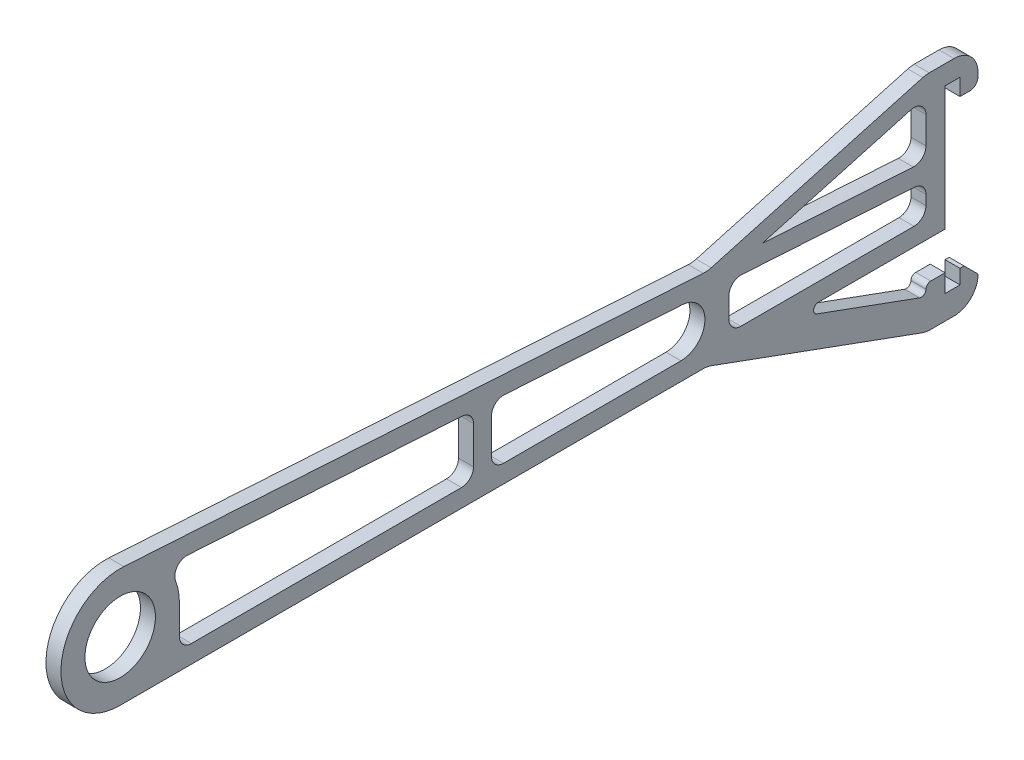
SolidWorks part; units mm, degrees
material "Delrin"
ref_plane "Front Plane" through (0, 0, 0) normal (0, 0, 1) x (1, 0, 0)
ref_plane "Top Plane" through (0, 0, 0) normal (0, 1, 0) x (1, 0, 0)
ref_plane "Right Plane" through (0, 0, 0) normal (1, 0, 0) x (0, 0, -1)
sketch "Sketch1" plane through (0, 0, 0) normal (1, 0, 0) x (0, 0, -1)
  line L0 (0.3859, 6.2619) -> (62.1851, 2.453)
  line L1 (0, -6.2738) -> (62.1851, -6.2738)
  line L2 (85.344, 8.8996) -> (88.3158, 8.8996)
  line L3 (4.7629, 4.0835) -> (85.344, -0.883)
  line L4 (4.5027, -4.3688) -> (85.344, -4.3688)
  line L5 (4.101, 4.1243) -> (87.7175, -1.0293) construction
  line L6 (0, -4.3688) -> (85.344, -4.3688) construction
  line L7 (85.344, -6.2738) -> (85.344, 8.8996) construction
  line L16 (6.2738, 0) -> (6.2738, -4.3688)
  line L17 (39.3251, 1.9533) -> (39.3251, -4.3688)
  line L18 (37.4201, 2.0707) -> (37.4201, -4.3688)
  line L23 (4.2182, 6.0257) -> (87.8347, 0.8721) construction
  line L24 (89.9668, 5.0896) -> (88.9508, 5.0896)
  line L25 (88.9508, 5.0896) -> (88.9508, 6.8676)
  line L26 (88.9508, 6.8676) -> (87.376, 6.8676)
  line L27 (87.376, 6.8676) -> (87.376, -6.2738)
  line L28 (87.376, -12.1824) -> (88.9508, -12.1824)
  line L29 (88.9508, -12.1824) -> (88.9508, -10.6584)
  line L30 (88.9508, -10.6584) -> (89.3826, -10.6584)
  line L31 (90.8558, -12.1316) -> (90.8558, -12.1824)
  line L32 (88.3158, -14.7224) -> (85.344, -14.7224)
  line L33 (85.344, -14.7224) -> (85.344, -6.2738) construction
  line L34 (90.8558, 5.9786) -> (90.8558, 6.3596)
  line L35 (89.3826, -10.6584) -> (90.8558, -12.1316)
  line L36 (64.4711, 0.4035) -> (64.4711, -4.3688)
  line L37 (62.1851, 0.5444) -> (62.1851, -4.3688)
  line L38 (62.1851, 2.453) -> (85.344, 8.8996)
  line L39 (68.0011, 2.0945) -> (85.344, 6.9222)
  line L40 (62.1851, -6.2738) -> (85.344, -14.7224)
  line L41 (71.0788, -6.2738) -> (85.344, -11.4779)
  line L42 (63.2297, -3.4104) -> (86.3886, -11.859) construction
  line L43 (62.696, 0.6178) -> (85.8549, 7.0644) construction
  line L44 (71.0788, -6.2738) -> (85.344, -6.2738)
  line L45 (0, -6.2738) -> (85.344, -6.2738) construction
  line L46 (68.0011, 2.0945) -> (85.344, 1.0256)
  line L47 (62.1851, -4.3688) -> (62.1851, 49995.6312) construction
  line L48 (85.344, 6.9222) -> (85.344, 1.0256)
  line L49 (85.344, -0.883) -> (85.344, -4.3688)
  line L50 (87.376, -12.1824) -> (87.376, -10.2774)
  line L51 (85.344, -6.2738) -> (87.376, -6.2738)
  line L52 (87.376, -10.2774) -> (85.344, -10.2774)
  line L53 (85.344, -10.2774) -> (85.344, -11.4779)
  circle A0 centre (0, 0) radius 3.7338
  circle A1 centre (0, 0) radius 6.2738
  arc A2 (88.3158, 8.8996) -> (90.8558, 6.3596) centre (88.3158, 6.3596) cw
  arc A3 (90.8558, -12.1824) -> (88.3158, -14.7224) centre (88.3158, -12.1824) cw
  arc A4 (90.8558, 5.9786) -> (89.9668, 5.0896) centre (89.9668, 5.9786) cw
  point P47 (90.8558, 8.8996)
  point P50 (90.8558, -14.7224)
  point P53 (90.8558, 5.0896)
  point P54 (90.8558, -10.6584)
  point P56 (90.8558, -10.6584)
  dimension "D1" = 7.4676
  dimension "D2" = 2.54
  dimension "D3" = 5.842
  dimension "D8" = 1.5748
  dimension "D18" = 2.54
  dimension "D19" = 2.54
  dimension "D20" = 0.889
  dimension "D21" = 22.86
  dimension "D5" = 37.4201
  dimension "D10" = 1.905
  dimension "D11" = 1.778
  dimension "D12" = 1.905
  dimension "D4" = 5.3842
  dimension "D9" = 1.5748
  dimension "D14" = 1.524
  dimension "D15" = 3.81
  dimension "D16" = 4.064
  dimension "D17" = 1.905
  dimension "D22" = 19.05
  dimension "D23" = 85.344
  dimension "D24" = 2.032
  dimension "D25" = 2.286
  dimension "D29" = 1.905
  dimension "D6" = 1.905
  dimension "D7" = 1.905
  dimension "D27" = 3.048
  dimension "D28" = 1.905
extrude "Boss-Extrude1" add sketch "Sketch1" along normal blind 1.5875 contours A1 L1 | A1 L4 L16 | L3 L18 L4 L17 | L31 L30 L29 L28 L27 L26 L25 L24 A4 L34 A2 L2 L7 L33 L32 A3 | A1 A0 | L3 L37 L4 L36 region at (0, 3.4205, -31.2278) region at (0, 5.4578, -2.7163) region at (0, -1.1783, -38.3697) region at (0, -3.3098, -5.7584) region at (0, -1.9473, -63.3226)
sketch "Sketch2" plane through (0, 0, -87.376) normal (0, 0, -1) x (-1, 0, 0)
  line L0 (-1.5875, 8.8996) -> (0, 8.8996) construction
  line L1 (-1.5875, 6.8676) -> (0, 6.8676) construction
  line L2 (-1.5875, -12.1824) -> (0, -12.1824) construction
  line L3 (-1.5875, -14.7224) -> (0, -14.7224) construction
  line L4 (-1.5875, 8.8996) -> (0, 8.8996)
  line L5 (-1.5875, 6.8676) -> (0, 6.8676)
  line L6 (-1.5875, -12.1824) -> (0, -12.1824)
  line L7 (-1.5875, -14.7224) -> (0, -14.7224)
  line L8 (-1.5875, 8.8996) -> (-1.5875, 6.8676)
  line L9 (0, 8.8996) -> (0, 6.8676)
  line L10 (-1.5875, -12.1824) -> (-1.5875, -14.7224)
  line L11 (0, -12.1824) -> (0, -14.7224)
fillet "Fillet1" radius 2.54 4 edges at (0.7937, 2.453, -62.1851) (0.7937, 8.8996, -85.344) (0.7937, -6.2738, -62.1851) (0.7937, -14.7224, -85.344)
fillet "Fillet2" radius 1.27 12 edges at (0.7937, 4.0835, -4.7629) (0.7937, -4.3688, -6.2738) (0.7937, -4.3688, -37.4201) (0.7937, 2.0707, -37.4201) (0.7937, -4.3688, -39.3251) (0.7937, 1.9533, -39.3251) (0.7937, 0.4035, -64.4711) (0.7937, -4.3688, -64.4711) (0.7937, 1.0256, -85.344) (0.7937, 6.9222, -85.344) (0.7937, -0.883, -85.344) (0.7937, -4.3688, -85.344)
fillet "Fillet3" radius 0.508 2 edges at (0.7937, -6.2738, -71.0788) (0.7937, -11.4779, -85.344)
fillet "Fillet4" radius 0.508 1 edges at (0.7937, -10.2774, -85.344)
sketch "Sketch4" plane through (1.5875, 0, 0) normal (1, 0, 0) x (0, 0, -1)
  line L0 (40.6732, 1.8702) -> (62.1851, 0.5444) construction
  line L1 (62.1851, 0.5444) -> (62.1851, -4.3688) construction
  line L2 (40.5951, -4.3688) -> (62.1851, -4.3688) construction
  line L3 (59.5471, 0.707) -> (62.1851, 0.5444)
  line L4 (62.1851, 0.5444) -> (62.1851, -4.3688)
  line L5 (59.3908, -4.3688) -> (62.1851, -4.3688)
  line L6 (61.9311, -1.8285) -> (62.1851, -1.8285) construction
  line L7 (87.376, 6.8676) -> (87.376, -6.2738) construction
  line L8 (40.5951, -4.3688) -> (62.1851, -4.3688) construction
  arc A0 (59.5471, 0.707) -> (59.3908, -4.3688) centre (59.3908, -1.8285) cw
  dimension "D1" = 0.254
extrude "Boss-Extrude2" add sketch "Sketch4" against normal up to surface (1.5875 mm away) up to face at (0, -0.6315, -20.0218)
